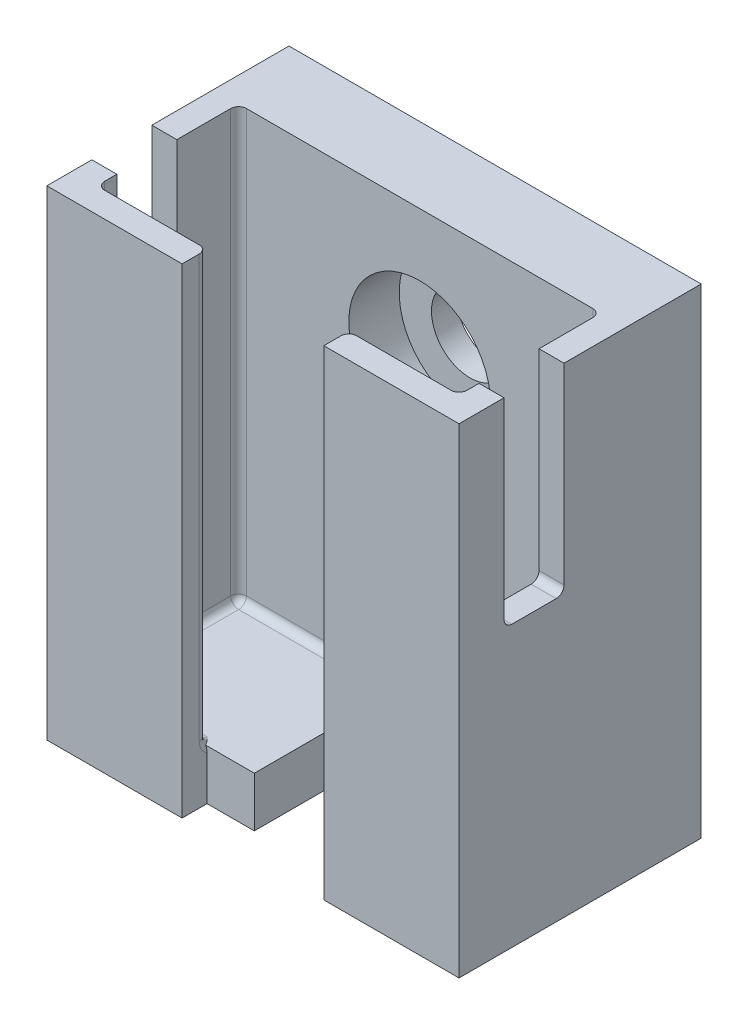
SolidWorks part; units mm, degrees
ref_plane "Front Plane" through (0, 0, 0) normal (0, 0, 1) x (1, 0, 0)
ref_plane "Top Plane" through (0, 0, 0) normal (0, 1, 0) x (1, 0, 0)
ref_plane "Right Plane" through (0, 0, 0) normal (1, 0, 0) x (0, 0, -1)
sketch "Sketch1" plane through (0, 0, 0) normal (0, 1, 0) x (1, 0, 0)
  line L0 (4.5, -6.1) -> (4.5, -7.6875)
  line L1 (-11.5, 6.1) -> (11.5, 6.1)
  line L2 (-11.5, 6.1) -> (-11.5, -6.1)
  line L3 (-11.5, -6.1) -> (-4.5, -6.1)
  line L4 (11.5, 6.1) -> (11.5, -6.1)
  line L5 (-11.5, 6.1) -> (11.5, -6.1) construction
  line L6 (-11.5, -6.1) -> (11.5, 6.1) construction
  line L7 (-13.088, -7.6875) -> (-4.5, -7.6875)
  line L8 (-13.088, -7.6875) -> (-13.088, 7.6875)
  line L9 (-13.088, 7.6875) -> (13.088, 7.6875)
  line L10 (13.088, -7.6875) -> (13.088, 7.6875)
  line L11 (-13.088, -7.6875) -> (13.088, 7.6875) construction
  line L12 (-13.088, 7.6875) -> (13.088, -7.6875) construction
  line L13 (0, -8.4563) -> (0, 8.4563) construction
  line L14 (-4.5, -6.1) -> (-4.5, -7.6875)
  line L15 (4.5, -7.6875) -> (13.088, -7.6875)
  line L16 (4.5, -6.1) -> (11.5, -6.1)
  point P0 (0, 0)
  point P6 (0, 0)
  dimension "D1" = 23
  dimension "D2" = 12.2
  dimension "D3" = 1.588
  dimension "D4" = 1.5875
  dimension "D5" = 4.5
extrude "Boss-Extrude1" add sketch "Sketch1" along normal blind 30.48
sketch "Sketch2" plane through (0, 0, 0) normal (0, -1, 0) x (1, 0, 0)
  line L5 (11.5, 6.1) -> (4.5, 6.1) construction
  line L11 (11.5, 0) -> (11.5, 6.1)
  line L12 (11.5, 6.1) -> (9.5, 6.1)
  line L13 (-1.5, 0) -> (9.5, 0)
  line L14 (-1.5, 0) -> (-1.5, 6.1)
  line L17 (-11.5, 6.1) -> (-1.5, 6.1)
  line L18 (-11.5, 6.1) -> (-11.5, -6.1)
  line L19 (-11.5, -6.1) -> (11.5, -6.1)
  line L20 (11.5, 0) -> (11.5, -6.1)
  line L21 (9.5, 0) -> (9.5, 6.1)
  dimension "D1" = 1.5
  dimension "D2" = 2
extrude "Boss-Extrude2" add sketch "Sketch2" against normal blind 3.175
sketch "Sketch3" plane through (0, 30.48, 0) normal (0, 1, 0) x (1, 0, 0)
  line L18 (-13.088, 7.6875) -> (-13.088, -7.6875) construction
  line L21 (-9.652, -1.02) -> (-13.088, -1.02)
  line L22 (-9.652, -1.02) -> (-9.652, -4.83)
  line L23 (-9.652, -4.83) -> (-13.088, -4.83)
  line L24 (-13.088, -1.02) -> (-13.088, -4.83)
  point P10 (-13.088, -2.925)
  dimension "D1" = 3.81
  dimension "D2" = 3.175
extrude "Cut-Extrude1" cut sketch "Sketch3" against normal blind 12.7
mirror "Mirror1" about plane through (0, 0, 0) normal (1, 0, 0) of "Cut-Extrude1"
sketch "Sketch5" plane through (0, 0, -7.6875) normal (0, 0, -1) x (-1, 0, 0)
  line L0 (8.4563, 0) -> (-8.4563, 0) construction
  line L1 (-13.088, 30.48) -> (13.088, 30.48) construction
  circle A0 centre (0, 8.4667) radius 2.45
  circle A1 centre (0, 22.0133) radius 2.45
  dimension "D1" = 4.9
  dimension "D2" = 4.9
  dimension "D3" = 8.4667
  dimension "D4" = 8.4667
extrude "Cut-Extrude2" cut sketch "Sketch5" against normal up to surface (1.5875 mm away) up to face at (0, 16.8275, -6.1)
sketch "Sketch6" plane through (0, 0, -6.1) normal (0, 0, 1) x (1, 0, 0)
  line L4 (-11.5, 3.175) -> (11.5, 3.175)
  line L6 (11.5, 3.175) -> (11.5, 30.48)
  line L7 (11.5, 30.48) -> (-11.5, 30.48)
  line L8 (-11.5, 30.48) -> (-11.5, 3.175)
  line L10 (11.5, 3.175) -> (11.5, 30.48)
  line L11 (11.5, 30.48) -> (-11.5, 30.48)
  line L12 (-11.5, 30.48) -> (-11.5, 3.175)
  line L14 (-11.5, 3.175) -> (11.5, 3.175)
  circle A0 centre (0, 22.0133) radius 4.5
  circle A1 centre (0, 8.4667) radius 4.5
  dimension "D1" = 9
  dimension "D2" = 9
  dimension "D3" = 0
extrude "Boss-Extrude3" add sketch "Sketch6" along normal blind 3.2
fillet "Fillet3" radius 0.5 4 edges at (0, 3.175, -2.9) (11.5, 16.8275, 6.1) (11.5, 16.8275, -2.9) (11.5, 3.175, 1.6)
fillet "Fillet1" radius 0.5 5 edges at (-11.5, 3.175, 1.85) (-8, 3.175, 6.1) (4.5, 15.24, 6.1) (-11.5, 17.0775, -2.9) (-11.5, 3.3214, -2.7536)
fillet "Fillet5" radius 0.5 6 edges at (-4.5, 17.0775, 6.1) (-4.5, 3.3214, 5.9536) (-12.294, 17.78, 4.83) (-12.294, 17.78, 1.02) (12.294, 17.78, 1.02) (12.294, 17.78, 4.83)
fillet "Fillet4" radius 0.5 2 edges at (-11.5, 17.0775, 6.1) (-11.3536, 3.3214, 5.9536)
fillet "Fillet6" radius 0.5 5 edges at (11.3536, 3.3214, 5.9536) (10.25, 3.175, 6.1) (9.5, 1.5875, 6.1) (9.5, 1.5875, 0) (-1.5, 1.5875, 0)
ref_plane "Plane1" through (0, 0, 2.925) normal (0, 0, 1) x (1, 0, 0)
